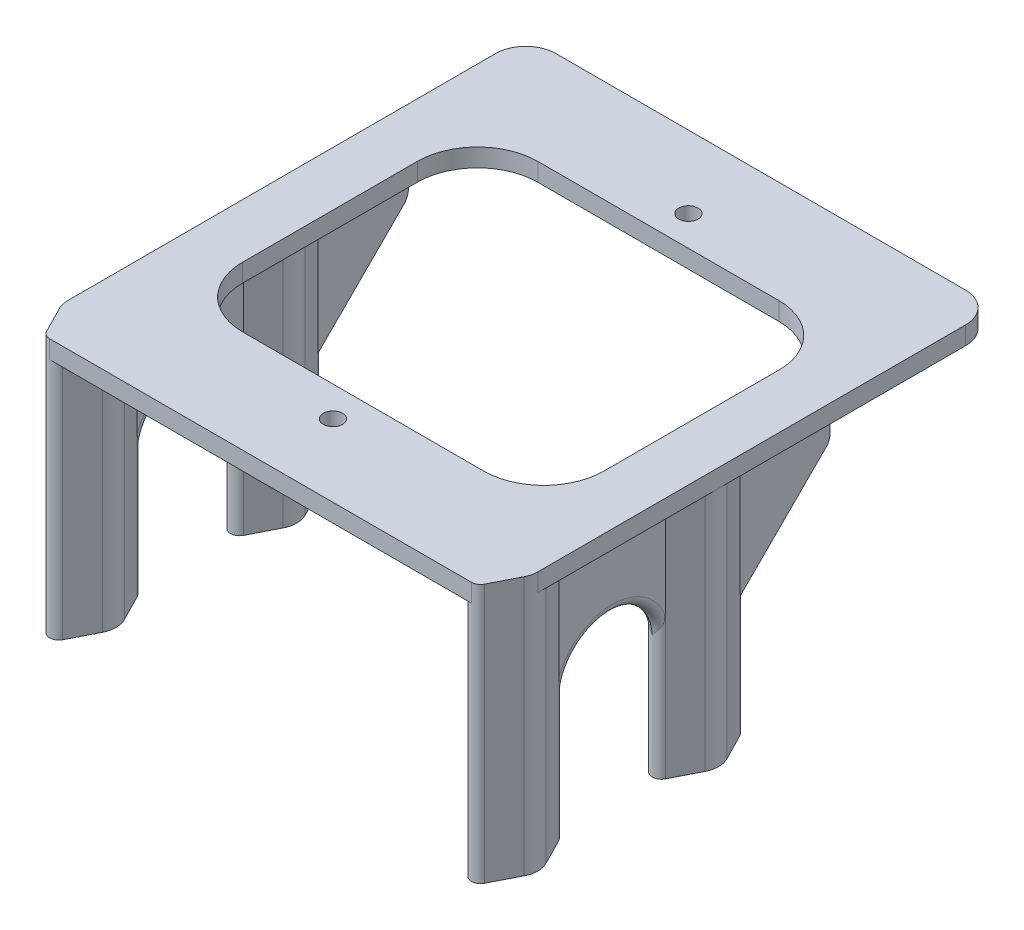
SolidWorks part; units mm, degrees
ref_plane "Front Plane" through (0, 0, 0) normal (0, 0, 1) x (1, 0, 0)
ref_plane "Top Plane" through (0, 0, 0) normal (0, 1, 0) x (1, 0, 0)
ref_plane "Right Plane" through (0, 0, 0) normal (1, 0, 0) x (0, 0, -1)
sketch "Sketch1" plane through (0, 0, 0) normal (0, 1, 0) x (1, 0, 0)
  line L0 (-1.3361, 6.1818) -> (-3.5629, 1.8182)
  line L1 (-3.5629, -1.8182) -> (-1.3361, -6.1818)
  line L2 (1.3361, -6.1818) -> (3.5629, -1.8182)
  line L3 (1.3361, 6.1818) -> (3.5629, 1.8182)
  line L4 (68.6639, 6.1818) -> (66.4371, 1.8182)
  line L5 (71.3361, 6.1818) -> (73.5629, 1.8182)
  line L6 (71.3361, -6.1818) -> (73.5629, -1.8182)
  line L7 (66.4371, -1.8182) -> (68.6639, -6.1818)
  line L8 (68.6639, -23.8182) -> (66.4371, -28.1818)
  line L9 (71.3361, -23.8182) -> (73.5629, -28.1818)
  line L10 (71.3361, -36.1818) -> (73.5629, -31.8182)
  line L11 (66.4371, -31.8182) -> (68.6639, -36.1818)
  line L12 (-1.3361, -23.8182) -> (-3.5629, -28.1818)
  line L13 (1.3361, -23.8182) -> (3.5629, -28.1818)
  line L14 (1.3361, -36.1818) -> (3.5629, -31.8182)
  line L15 (-3.5629, -31.8182) -> (-1.3361, -36.1818)
  circle A0 centre (0, 0) radius 1.6
  circle A1 centre (70, 0) radius 1.6
  circle A2 centre (0, -30) radius 1.6
  circle A3 centre (70, -30) radius 1.6
  arc A4 (-3.5629, 1.8182) -> (-3.5629, -1.8182) centre (0, 0) ccw
  arc A5 (1.3361, 6.1818) -> (-1.3361, 6.1818) centre (0, 5.5) ccw
  arc A6 (-1.3361, -6.1818) -> (1.3361, -6.1818) centre (0, -5.5) ccw
  arc A7 (3.5629, -1.8182) -> (3.5629, 1.8182) centre (0, 0) ccw
  arc A8 (71.3361, 6.1818) -> (68.6639, 6.1818) centre (70, 5.5) ccw
  arc A9 (73.5629, -1.8182) -> (73.5629, 1.8182) centre (70, 0) ccw
  arc A10 (68.6639, -6.1818) -> (71.3361, -6.1818) centre (70, -5.5) ccw
  arc A11 (66.4371, 1.8182) -> (66.4371, -1.8182) centre (70, 0) ccw
  arc A12 (71.3361, -23.8182) -> (68.6639, -23.8182) centre (70, -24.5) ccw
  arc A13 (73.5629, -31.8182) -> (73.5629, -28.1818) centre (70, -30) ccw
  arc A14 (68.6639, -36.1818) -> (71.3361, -36.1818) centre (70, -35.5) ccw
  arc A15 (66.4371, -28.1818) -> (66.4371, -31.8182) centre (70, -30) ccw
  arc A16 (1.3361, -23.8182) -> (-1.3361, -23.8182) centre (0, -24.5) ccw
  arc A17 (3.5629, -31.8182) -> (3.5629, -28.1818) centre (0, -30) ccw
  arc A18 (-1.3361, -36.1818) -> (1.3361, -36.1818) centre (0, -35.5) ccw
  arc A19 (-3.5629, -28.1818) -> (-3.5629, -31.8182) centre (0, -30) ccw
  dimension "D2" = 3.2
  dimension "D4" = 3
  dimension "D5" = 8
  dimension "D1" = 30
  dimension "D3" = 70
  dimension "D6" = 2
  dimension "D7" = 2
extrude "Boss-Extrude1" add sketch "Sketch1" along normal blind 40
sketch "Sketch2" plane through (0, 40, 0) normal (0, 1, 0) x (1, 0, 0)
  line L1 (1, 46) -> (69, 46)
  line L2 (-4, 41) -> (-4, -30)
  line L3 (0, -37) -> (70, -37)
  line L4 (74, 41) -> (74, -30)
  line L7 (71.3361, -36.1818) -> (73.5629, -31.8182)
  line L8 (-3.5629, -31.8182) -> (-1.3361, -36.1818)
  line L9 (-3.5629, -31.8182) -> (-1.3361, -36.1818)
  line L10 (71.3361, -36.1818) -> (73.5629, -31.8182)
  line L11 (15, 29) -> (55, 29)
  line L12 (5, 19) -> (5, -10)
  line L13 (15, -20) -> (55, -20)
  line L14 (65, 19) -> (65, -10)
  circle A0 centre (35, -25) radius 1.6
  circle A1 centre (35, 34) radius 1.6
  circle A2 centre (70, 0) radius 1.6 construction
  arc A3 (73.5629, -31.8182) -> (73.5629, -28.1818) centre (70, -30) ccw construction
  arc A4 (-3.5629, -28.1818) -> (-3.5629, -31.8182) centre (0, -30) ccw construction
  arc A5 (-1.3361, -36.1818) -> (1.3361, -36.1818) centre (0, -35.5) ccw construction
  circle A6 centre (0, 0) radius 1.6 construction
  arc A7 (55, -20) -> (65, -10) centre (55, -10) ccw
  arc A8 (5, -10) -> (15, -20) centre (15, -10) ccw
  arc A9 (55, 29) -> (65, 19) centre (55, 19) cw
  arc A10 (15, 29) -> (5, 19) centre (15, 19) ccw
  arc A11 (73.5629, -31.8182) -> (73.5629, -28.1818) centre (70, -30) ccw
  arc A12 (-1.3361, -36.1818) -> (1.3361, -36.1818) centre (0, -35.5) ccw
  arc A13 (-3.5629, -28.1818) -> (-3.5629, -31.8182) centre (0, -30) ccw
  arc A14 (-1.3361, -36.1818) -> (0, -37) centre (0, -35.5) ccw
  arc A15 (-4, -30) -> (-3.5629, -31.8182) centre (0, -30) ccw
  arc A16 (68.6639, -36.1818) -> (71.3361, -36.1818) centre (70, -35.5) ccw
  arc A17 (73.5629, -31.8182) -> (74, -30) centre (70, -30) ccw
  arc A18 (70, -37) -> (71.3361, -36.1818) centre (70, -35.5) ccw
  arc A19 (69, 46) -> (74, 41) centre (69, 41) cw
  arc A20 (1, 46) -> (-4, 41) centre (1, 41) ccw
  point P8 (35, 46)
  dimension "D1" = 3.2
  dimension "D11" = 10
  dimension "D12" = 5
  dimension "D2" = 59
  dimension "D5" = 12
  dimension "D6" = 12
  dimension "D7" = 5
  dimension "D8" = 5
  dimension "D9" = 5
  dimension "D10" = 5
  dimension "D3" = 0
  dimension "D4" = 0
extrude "Boss-Extrude2" add sketch "Sketch2" along normal blind 3
sketch "Sketch4" plane through (0, 40, 0) normal (0, -1, 0) x (1, 0, 0)
  line L1 (-1.3361, -6.1818) -> (1.3361, -6.1818)
  line L2 (-1.3361, -6.1818) -> (-1.3361, -21.1818)
  line L3 (-1.3361, -21.1818) -> (1.3361, -21.1818)
  line L4 (1.3361, -6.1818) -> (1.3361, -21.1818)
  line L5 (-1.3361, 23.8182) -> (1.3361, 23.8182)
  line L6 (-1.3361, 23.8182) -> (-1.3361, 6.1818)
  line L7 (-1.3361, 6.1818) -> (1.3361, 6.1818)
  line L8 (1.3361, 23.8182) -> (1.3361, 6.1818)
  dimension "D1" = 15
extrude "Boss-Extrude3" add sketch "Sketch4" along normal blind 20
ref_plane "Plane1" through (65, 43, -19) normal (0, 0, -1) x (-1, 0, 0)
sketch "Sketch6" plane through (-1.3361, 0, 0) normal (-1, 0, 0) x (0, 0, 1)
  line L0 (23.8182, 20) -> (6.1818, 20) construction
  line L1 (23, 20) -> (23, 0) construction
  circle A0 centre (15, 20) radius 8
extrude "Cut-Extrude2" cut sketch "Sketch6" against normal through all contours A0
fillet "Fillet1" radius 1.5 2 edges at (1.3361, 28, 15) (-1.3361, 28, 15)
chamfer "Chamfer1" distance 15 angle 45 1 edges at (0, 20, -21.1818)
ref_plane "Plane2" through (35, 0, 0) normal (-1, 0, 0) x (0, 0, 1)
mirror "Mirror1" about plane through (35, 0, 0) normal (-1, 0, 0) of "Chamfer1", "Cut-Extrude2", "Boss-Extrude3", "Fillet1"
fillet "Fillet2" radius 2.5 4 edges at (70, 40, -21.1818) (0, 40, -21.1818) (70, 35, -21.1818) (0, 35, -21.1818)
sketch "Sketch7" plane through (0, 40, 0) normal (0, -1, 0) x (1, 0, 0)
  circle A14 centre (0, 30) radius 1.6
  circle A15 centre (0, 0) radius 1.6
  circle A16 centre (70, 0) radius 1.6
  circle A17 centre (70, 30) radius 1.6
  dimension "D1" = 3.2
extrude "Boss-Extrude4" add sketch "Sketch7" along normal blind 20
